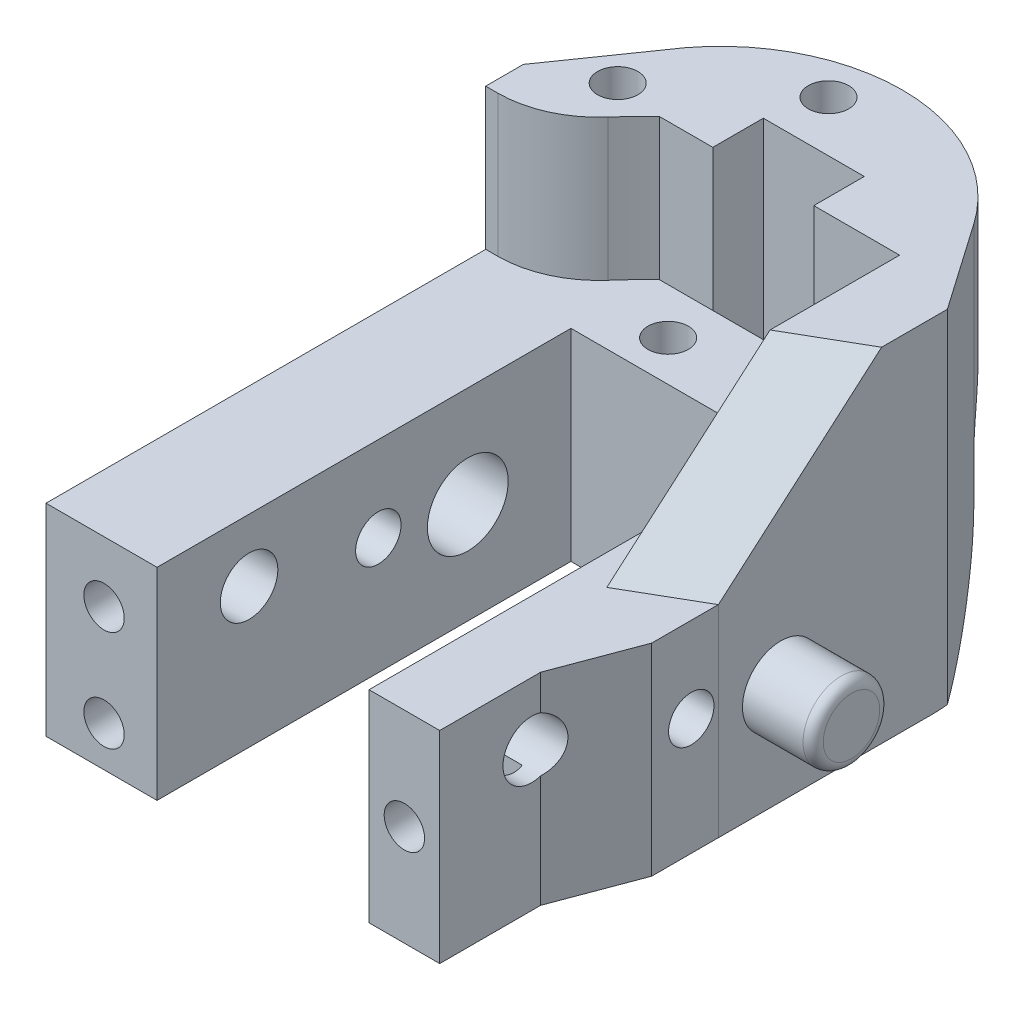
SolidWorks part; units mm, degrees
material "ABS"
ref_plane "Front Plane" through (0, 0, 0) normal (0, 0, 1) x (1, 0, 0)
ref_plane "Top Plane" through (0, 0, 0) normal (0, 1, 0) x (1, 0, 0)
ref_plane "Right Plane" through (0, 0, 0) normal (1, 0, 0) x (0, 0, -1)
sketch "Sketch1" plane through (0, 0, 0) normal (0, 1, 0) x (1, 0, 0)
  line L0 (-15.5, -37) -> (-10, -37)
  line L2 (-15.5, -37) -> (-15.5, 10)
  line L3 (-15.5, 10) -> (21, 10)
  line L4 (21, -19) -> (21, 10)
  line L5 (-10, -37) -> (-10, 4)
  line L6 (-10, 4) -> (11, 4)
  line L7 (11, 4) -> (11, -37)
  line L9 (21, -19) -> (18, -27)
  line L10 (18, -27) -> (18, -37)
  line L11 (11, -37) -> (18, -37)
  point P0 (0, 0)
  dimension "D1" = 36.5
  dimension "D2" = 7
  dimension "D3" = 21
  dimension "D4" = 10
  dimension "D5" = 21
  dimension "D6" = 41
  dimension "D7" = 47
  dimension "D8" = 8
  dimension "D9" = 5.5
  dimension "D10" = 10
extrude "Boss-Extrude1" add sketch "Sketch1" along normal blind 20
sketch "Sketch6" plane through (-15.5, 0, 0) normal (-1, 0, 0) x (0, 0, 1)
  line L1 (15, 0) -> (-10, 0)
  line L2 (15, 0) -> (15, 20)
  line L3 (15, 20) -> (-10, 20)
  line L4 (-10, 0) -> (-10, 20)
  line L5 (-10, 20) -> (-10, 0) construction
  line L7 (-10, 0) -> (37, 0) construction
  line L8 (-10, 20) -> (37, 20) construction
  dimension "D3" = 25
extrude "Boss-Extrude5" add sketch "Sketch6" along normal blind 5.5
sketch "Sketch20" plane through (0, 20, 0) normal (0, 1, 0) x (1, 0, 0)
  line L4 (-21, 6.5542) -> (14, 6.5542)
  line L11 (21.0063, -12.4007) -> (21.0063, 10.2821)
  line L12 (21.0063, 10.2821) -> (15.0032, 18.9016)
  line L13 (15.0032, 18.9016) -> (-14.9968, 18.9016)
  line L14 (-14.9968, 18.9016) -> (-21, 10.2821)
  line L15 (-21, 10) -> (-21, -15) construction
  line L16 (-21, 10.2821) -> (-21, 6.5542)
  line L18 (14, 6.5542) -> (14, -16.4458)
  line L20 (14, -16.4458) -> (21.0063, -12.4007)
  dimension "D2" = 23
  dimension "D4" = 30
  dimension "D8" = 35
  dimension "D9" = 60
  dimension "D1" = 6.0032
  dimension "D3" = 6.0032
  dimension "D5" = 8.6195
  dimension "D6" = 8.6195
  dimension "D7" = 3.7279
extrude "Boss-Extrude11" add sketch "Sketch20" along normal blind 14 and the other way up to surface (20 mm away) other way up to face at (0.5833, 0, 16.3333)
sketch "Sketch4" plane through (0, 20, 0) normal (0, 1, 0) x (1, 0, 0)
  line L2 (-10, 4) -> (11, 4) construction
  line L4 (-10, -37) -> (-10, 4) construction
  circle A6 centre (-4.375, 8) radius 2
  circle A7 centre (5.375, 8) radius 2
  dimension "D1" = 4
  dimension "D2" = 4
  dimension "D3" = 9.75
  dimension "D4" = 5.625
extrude "Cut-Extrude1" cut sketch "Sketch4" against normal blind 10
sketch "Sketch24" plane through (0, 34, 0) normal (0, 1, 0) x (1, 0, 0)
  line L0 (21.0063, 10.2821) -> (15.0032, 18.9016) construction
  line L1 (-14.9968, 18.9016) -> (-14.4209, 19.7285)
  line L2 (-21, 10.2821) -> (-21, 6.5542) construction
  line L3 (-14.9968, 18.9016) -> (-21, 10.2821) construction
  line L4 (21.0063, 10.2821) -> (15.0032, 18.9016)
  line L6 (-21, 10.2821) -> (-21, 6.5542)
  line L7 (-14.9968, 18.9016) -> (-21, 10.2821)
  line L11 (-21, 6.5542) -> (14, 6.5542) construction
  line L14 (-21, 6.5542) -> (21.0063, 6.5542)
  line L16 (21.0063, 10.2821) -> (21.0063, 6.5542)
  line L17 (21.0063, -12.4007) -> (21.0063, 10.2821) construction
  arc A3 (8.6131, 24.6437) -> (-14.4209, 19.7285) centre (-0.0555, 8.8374) ccw
  arc A4 (8.6131, 24.6437) -> (15.0032, 18.9016) centre (-0.4313, 8.152) cw
  dimension "D3" = 18.0273
  dimension "D4" = 18.8089
  dimension "D1" = 0.5759
  dimension "D2" = 1.0077
extrude "Boss-Extrude13" add sketch "Sketch24" against normal blind 12
fillet "Fillet11" radius 7.95 1 edges at (0.0032, 22, -18.9016)
sketch "Sketch22" plane through (0, 34, 0) normal (0, 1, 0) x (1, 0, 0)
  line L2 (-21, 10.2821) -> (-21, 6.5542) construction
  line L3 (-21, 6.5542) -> (14, 6.5542) construction
  circle A0 centre (-14.7203, 13.3514) radius 2
  circle A1 centre (-3.0673, 22.5813) radius 2
  dimension "D1" = 4
  dimension "D2" = 6.2797
  dimension "D3" = 6.7972
  dimension "D4" = 17.9327
  dimension "D5" = 16.0271
extrude "Cut-Extrude6" cut sketch "Sketch22" against normal blind 10
chamfer "Chamfer1" distance 14 angle 45 1 edges at (17.5032, 34, 14.4233)
sketch "Sketch26" plane through (-21, 0, 0) normal (-1, 0, 0) x (0, 0, 1)
  line L0 (15, 0) -> (37, 0)
  line L2 (37, 0) -> (37, 20)
  line L3 (37, 20) -> (15, 20)
  line L4 (15, 0) -> (15, 20) construction
  line L5 (15, 20) -> (15, 0)
extrude "Boss-Extrude14" add sketch "Sketch26" against normal up to surface (11 mm away) up to face at (-10, 10, 16.5)
sketch "Sketch25" plane through (-21, 0, 0) normal (-1, 0, 0) x (0, 0, 1)
  line L0 (11.8689, 14.9312) -> (31.15, 18.331)
  line L1 (13.2147, 7.2989) -> (32.4958, 10.6987)
  line L2 (32.4958, 10.6987) -> (31.15, 18.331) construction
  line L3 (6.2179, 10) -> (31.8229, 14.5149) construction
  line L4 (-10.2821, 0) -> (37, 0) construction
  line L5 (6.2179, 10) -> (6.2179, 38.8588) construction
  line L7 (-10.2821, 34) -> (-10.2821, 0) construction
  arc A1 (11.8689, 14.9312) -> (13.2147, 7.2989) centre (6.2179, 10) ccw
  arc A3 (31.15, 18.331) -> (32.4958, 10.6987) centre (31.8229, 14.5149) cw
  point P4 (0, 0)
  dimension "D2" = 7.75
  dimension "D1" = 7.5
  dimension "D4" = 7.75
  dimension "D3" = 26
  dimension "D5" = 80
  dimension "D7" = 10
  dimension "D6" = 16.5
  dimension "D8" = 3.875
extrude "Cut-Extrude7" cut sketch "Sketch25" against normal blind 2.5
sketch "Sketch27" plane through (-18.5, 0, 0) normal (-1, 0, 0) x (0, 0, 1)
  line L0 (6.2179, 10) -> (31.8229, 14.5149) construction
  circle A0 centre (6.2179, 10) radius 4
  circle A1 centre (15.0812, 11.5628) radius 1.15
  circle A4 centre (27.8837, 13.8203) radius 1.6
  dimension "D1" = 8
  dimension "D3" = 2.3
  dimension "D4" = 3.2
  dimension "D2" = 9
  dimension "D5" = 4
extrude "Cut-Extrude8" cut sketch "Sketch27" against normal up to next
sketch "Sketch28" plane through (-21, 0, 0) normal (-1, 0, 0) x (0, 0, 1)
  line L4 (-0.0283, 0.7779) -> (-3.1977, 15.9504)
  line L6 (13.3704, 7.7433) -> (11.8689, 14.9312) construction
  line L10 (-3.1977, 15.9504) -> (10.5064, 18.8131)
  line L11 (10.5064, 18.8131) -> (17.2487, 15.8798)
  line L13 (31.15, 18.331) -> (11.8689, 14.9312) construction
  line L14 (17.2487, 15.8798) -> (18.6801, 9.0277)
  line L16 (18.6801, 9.0277) -> (13.6759, 3.6406)
  line L17 (13.6759, 3.6406) -> (-0.0283, 0.7779)
  arc A0 (11.8689, 14.9312) -> (13.2147, 7.2989) centre (6.2179, 10) ccw construction
  circle A1 centre (6.2179, 10) radius 4 construction
  point P8 (0, 0)
  point P9 (13.1947, 3.1782)
  point P18 (21.9096, 9.2129)
  dimension "D1" = 15.5
  dimension "D2" = 7.75
  dimension "D3" = 8
  dimension "D4" = 14
  dimension "D5" = 14
  dimension "D6" = 6
  dimension "D7" = 7
extrude "Cut-Extrude9" cut sketch "Sketch28" against normal blind 2.5
sketch "Sketch31" plane through (-18.5, 0, 0) normal (-1, 0, 0) x (0, 0, 1)
  circle A0 centre (6.2179, 10) radius 4
  circle A1 centre (6.2179, 10) radius 1.65
  circle A2 centre (6.2179, 10) radius 4 construction
  dimension "D2" = 3.3
extrude "Boss-Extrude15" add sketch "Sketch31" along normal blind 1 and the other way blind 2
sketch "Sketch32" plane through (-10, 0, 0) normal (1, 0, 0) x (0, 0, -1)
  circle A0 centre (-27.8837, 13.8203) radius 2.85
  circle A3 centre (-15.0812, 11.5628) radius 2.25
  dimension "D1" = 5.7
  dimension "D2" = 4.5
extrude "Cut-Extrude12" cut sketch "Sketch32" against normal blind 7 and the other way up to next
sketch "Sketch33" plane through (21.0063, 0, 0) normal (1, 0, 0) x (0, 0, -1)
  circle A0 centre (-6.2179, 10) radius 3.8
  circle A1 centre (-6.2179, 10) radius 1.65 construction
  dimension "D1" = 7.6
extrude "Boss-Extrude17" add sketch "Sketch33" along normal blind 7
fillet "Fillet17" radius 1 1 edges at (28.0063, 10, 2.4179)
sketch "Sketch35" plane through (0, 34, 0) normal (0, 1, 0) x (1, 0, 0)
  line L0 (-21, 6.5542) -> (14, 6.5542) construction
  line L1 (-19.8, 6.5542) -> (14, 6.5542)
  line L3 (-9.8027, 12.5542) -> (14, 12.5542)
  line L4 (14, 6.5542) -> (14, 12.5542)
  line L7 (14, 6.5542) -> (14, -0.28) construction
  arc A0 (-19.8, 6.5542) -> (-12.285, 9.9568) centre (-19.8, 16.5542) ccw
  arc A1 (-12.285, 9.9568) -> (-9.8027, 12.5542) centre (19.6614, -18.0889) cw
  dimension "D3" = 42.5104
  dimension "D4" = 10
  dimension "D5" = 8.2494
  dimension "D1" = 23.8027
  dimension "D2" = 6
  dimension "D6" = 9.9972
extrude "Cut-Extrude13" cut sketch "Sketch35" against normal up to surface (14 mm away) up to face at (4.25, 20, 11.0396)
sketch "Sketch36" plane through (0, 0, 37) normal (0, 0, 1) x (1, 0, 0)
  line L0 (11, 20) -> (11, 0) construction
  line L1 (11, 20) -> (18, 20) construction
  line L2 (-21, 0) -> (-21, 20) construction
  line L6 (-21, 20) -> (-10, 20) construction
  circle A0 centre (-15.25, 14) radius 2
  circle A1 centre (14.5, 10) radius 2
  circle A2 centre (-15.25, 4) radius 2
  dimension "D3" = 4
  dimension "D1" = 5.75
  dimension "D2" = 3.5
  dimension "D4" = 10
  dimension "D5" = 6
  dimension "D6" = 5.75
  dimension "D7" = 10
extrude "Cut-Extrude14" cut sketch "Sketch36" against normal blind 10
fillet "Fillet18" radius 10 1 edges at (0.0032, 0, -18.9016)
sketch "Sketch37" plane through (21, 0, 0) normal (1, 0, 0) x (0, 0, -1)
  line L0 (-6.2179, 10) -> (6.304, 10) construction
  line L1 (4, 20) -> (4, 0) construction
  line L2 (-1.7179, 13) -> (4, 13)
  line L3 (-1.7179, 13) -> (-1.7179, 7)
  line L4 (-1.7179, 7) -> (4, 7)
  line L5 (4, 13) -> (4, 7)
  point P7 (0.043, 10)
  dimension "D1" = 6
  dimension "D2" = 3
  dimension "D4" = 4.5
extrude "Cut-Extrude16" cut sketch "Sketch37" against normal up to next
chamfer "Chamfer2" distance 7 angle 45 1 edges at (11, 10, 1.7179)
sketch "Sketch38" plane through (0, 0, 0) normal (0, -1, 0) x (1, 0, 0)
  line L0 (-10, -4) -> (11, -4) construction
  line L1 (-4.5, -4) -> (5.5, -4)
  line L2 (-4.5, -4) -> (-4.5, -24)
  line L3 (-4.5, -24) -> (5.5, -24)
  line L4 (5.5, -4) -> (5.5, -24)
  line L5 (-10, 37) -> (-10, -4) construction
  dimension "D1" = 10
  dimension "D2" = 5.5
  dimension "D3" = 20
extrude "Cut-Extrude17" cut sketch "Sketch38" against normal blind 4
sketch "Sketch39" plane through (0, 34, 0) normal (0, 1, 0) x (1, 0, 0)
  line L0 (14, 12.5542) -> (-9.8027, 12.5542) construction
  line L1 (-4.5, 12.5542) -> (5.5, 12.5542)
  line L2 (-4.5, 12.5542) -> (-4.5, 17.5542)
  line L3 (-4.5, 17.5542) -> (5.5, 17.5542)
  line L4 (5.5, 12.5542) -> (5.5, 17.5542)
  line L5 (5.5, 16.9016) -> (5.5, 4) construction
  line L6 (-4.5, 4) -> (-4.5, 16.9016) construction
  dimension "D1" = 5
extrude "Cut-Extrude19" cut sketch "Sketch39" against normal up to next
equation "\"D4@Sketch4\"=(21-\"D3@Sketch4\")/2"
equation "\"D2@Sketch37\"=\"D1@Sketch37\"/2"
equation "\"D3@Sketch20\"=\"D1@Sketch20\""
equation "\"D6@Sketch20\"=\"D5@Sketch20\""
equation "\"D5@Sketch28\"=\"D4@Sketch28\""
equation "\"D2@Sketch25\"=\"D4@Sketch25\""
equation "\"D8@Sketch25\"=\"D4@Sketch25\"/2"
